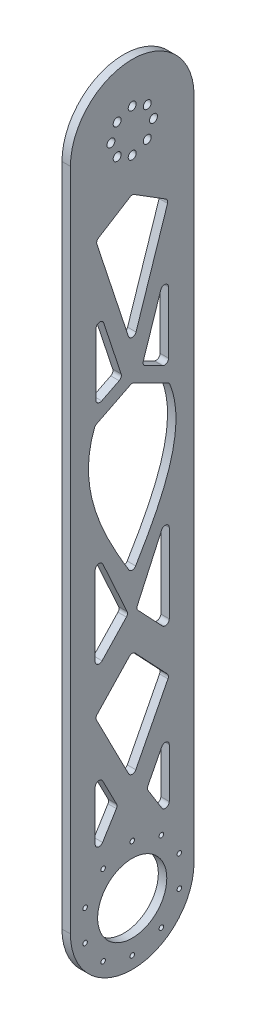
SolidWorks part; units mm, degrees
material "1060 Alloy"
ref_plane "Front Plane" through (0, 0, 0) normal (0, 0, 1) x (1, 0, 0)
ref_plane "Top Plane" through (0, 0, 0) normal (0, 1, 0) x (1, 0, 0)
ref_plane "Right Plane" through (0, 0, 0) normal (1, 0, 0) x (0, 0, -1)
sketch "Sketch1" plane through (0, 0, 0) normal (1, 0, 0) x (0, -1, 0)
  line L0 (0, 0) -> (500, 0) construction
  line L1 (0, 46.5) -> (500, 46.5)
  line L2 (0, -46.5) -> (500, -46.5)
  arc A0 (0, 46.5) -> (0, -46.5) centre (0, 0) ccw
  arc A1 (500, -46.5) -> (500, 46.5) centre (500, 0) ccw
  circle A2 centre (0, 0) radius 16 construction
  circle A3 centre (-16, 0) radius 3
  circle A4 centre (-11.3137, 11.3137) radius 3
  circle A5 centre (0, 16) radius 3
  circle A6 centre (11.3137, 11.3137) radius 3
  circle A7 centre (16, 0) radius 3
  circle A8 centre (11.3137, -11.3137) radius 3
  circle A27 centre (500, 0) radius 37.25 construction
  circle A28 centre (537.25, 0) radius 1.7
  circle A29 centre (500, 0) radius 37.25 construction
  circle A30 centre (537.25, 0) radius 1.7
  circle A31 centre (530.1359, -21.895) radius 1.7
  circle A32 centre (511.5109, -35.4269) radius 1.7
  circle A33 centre (488.4891, -35.4269) radius 1.7
  circle A34 centre (469.8641, -21.895) radius 1.7
  circle A35 centre (462.75, 0) radius 1.7
  circle A36 centre (469.8641, 21.895) radius 1.7
  circle A37 centre (488.4891, 35.4269) radius 1.7
  circle A38 centre (511.5109, 35.4269) radius 1.7
  circle A39 centre (530.1359, 21.895) radius 1.7
  circle A40 centre (500, 0) radius 26
  circle A41 centre (0, -16) radius 3
  circle A42 centre (-11.3137, -11.3137) radius 3
  point P3 (250, 0)
  point P25 (0, 0)
  point P52 (500, 0)
  point P61 (500, 0)
  dimension "D3" = 32
  dimension "D4" = 6
  dimension "D2" = 74.5
  dimension "D7" = 3.4
  dimension "D8" = 3.4
  dimension "D10" = 52
  dimension "D6" = 46.5
  dimension "D1" = 500
  dimension "D5" = 8
  dimension "D9" = 10
extrude "Boss-Extrude1" add sketch "Sketch1" along normal blind 6.35 contours L2 A1 L1 A0 A40 A39 A38 A37 A36 A35 A34 A33 A32 A31 A28 A8 A7 A6 A5 A4 A3 region at (0, -240.225, 0)
ref_axis "Axis1" through (6.35, -500, 0) along (-1, 0, 0)
sketch "Sketch3" plane through (6.35, 0, 0) normal (1, 0, 0) x (0, 0, -1)
  line L0 (0, -500) -> (0, 0) construction
  line L1 (0, -422.848) -> (27.8582, -368.6328)
  line L2 (0, -422.848) -> (-27.8582, -368.6328)
  line L3 (-27.8582, -368.6328) -> (0, -339.1393)
  line L4 (0, -339.1393) -> (27.8582, -368.6328)
  line L5 (0, -41.3687) -> (-27.3129, -58.4352)
  line L6 (-27.3129, -58.4352) -> (0, -141.249)
  line L7 (0, -141.249) -> (27.3129, -58.4352)
  line L8 (27.3129, -58.4352) -> (0, -41.3687)
  line L9 (3, -313.1891) -> (27.8582, -339.5065)
  line L10 (27.8582, -339.5065) -> (27.8582, -258.646)
  line L11 (27.8582, -258.646) -> (3, -313.1891)
  line L12 (-27.8582, -339.5065) -> (-27.8582, -258.646)
  line L13 (-3, -313.1891) -> (-27.8582, -339.5065)
  line L14 (-27.8582, -258.646) -> (-3, -313.1891)
  line L15 (-27.8582, -401.4529) -> (-11, -434.2608)
  line L16 (-11, -434.2608) -> (-27.8582, -461.4818)
  line L17 (-27.8582, -461.4818) -> (-27.8582, -401.4529)
  line L18 (11, -434.2608) -> (27.8582, -461.4818)
  line L19 (27.8582, -401.4529) -> (11, -434.2608)
  line L20 (27.8582, -461.4818) -> (27.8582, -401.4529)
  line L21 (0, -164.2489) -> (-27.8582, -178.2005)
  line L22 (0, -164.2489) -> (27.8582, -178.2005)
  line L23 (7.5, -156.821) -> (27.3129, -96.7475)
  line L24 (27.3129, -96.7475) -> (27.3129, -166.7434)
  line L25 (27.3129, -166.7434) -> (7.5, -156.821)
  line L26 (-27.3129, -96.7475) -> (-27.3129, -166.7434)
  line L27 (-7.5, -156.821) -> (-27.3129, -96.7475)
  line L28 (-27.3129, -166.7434) -> (-7.5, -156.821)
  spline S0 degree 3 poles (-27.8582, -178.2005) (-43.7791, -216.0933) (-18.6166, -258.2761) (0, -289.085) knots 0 0 0 0 1 1 1 1
  spline S1 degree 3 poles (27.8582, -178.2005) (43.7791, -216.0933) (18.6166, -258.2761) (0, -289.085) knots 0 0 0 0 1 1 1 1
  point P32 (28.084, -107.6268)
  point P34 (0, 0)
  point P38 (-27.3129, -58.4352)
  point P39 (0, 0)
  point P42 (-27.8582, -368.6328)
  dimension "D1" = 15
  dimension "D2" = 20
  dimension "D3" = 12
  dimension "D4" = 10
  dimension "D5" = 6
  dimension "D6" = 15
  dimension "D7" = 22
extrude "Cut-Extrude1" cut sketch "Sketch3" against normal through all
fillet "Fillet1" radius 3 30 edges at (3.175, -58.4352, -27.3129) (3.175, -41.3687, 0) (3.175, -58.4352, 27.3129) (3.175, -141.249, 0) (3.175, -289.085, 0) (3.175, -164.2489, 0) (3.175, -401.4529, 27.8582) (3.175, -434.2608, 11) (3.175, -461.4818, 27.8582) (3.175, -461.4818, -27.8582) (3.175, -434.2608, -11) (3.175, -401.4529, -27.8582) (3.175, -368.6328, -27.8582) (3.175, -339.1393, 0) (3.175, -368.6328, 27.8582) (3.175, -422.848, 0) (3.175, -313.1891, 3) (3.175, -339.5065, 27.8582) (3.175, -258.646, 27.8582) (3.175, -178.2005, -27.8582) (3.175, -178.2005, 27.8582) (3.175, -339.5065, -27.8582) (3.175, -313.1891, -3) (3.175, -258.646, -27.8582) (3.175, -96.7475, 27.3129) (3.175, -166.7434, 27.3129) (3.175, -156.821, 7.5) (3.175, -166.7434, -27.3129) (3.175, -156.821, -7.5) (3.175, -96.7475, -27.3129)
equation "\"L1L\"=500"
equation "\"D1@Sketch1\"=\"L1L\""
equation "\"L1Thick\"=6.35"
equation "\"D1@Boss-Extrude1\"=\"L1Thick\""
equation "\"Harm-Drive-Outer\"=74.5"
equation "\"D2@Sketch1\"=\"Harm-Drive-Outer\""
